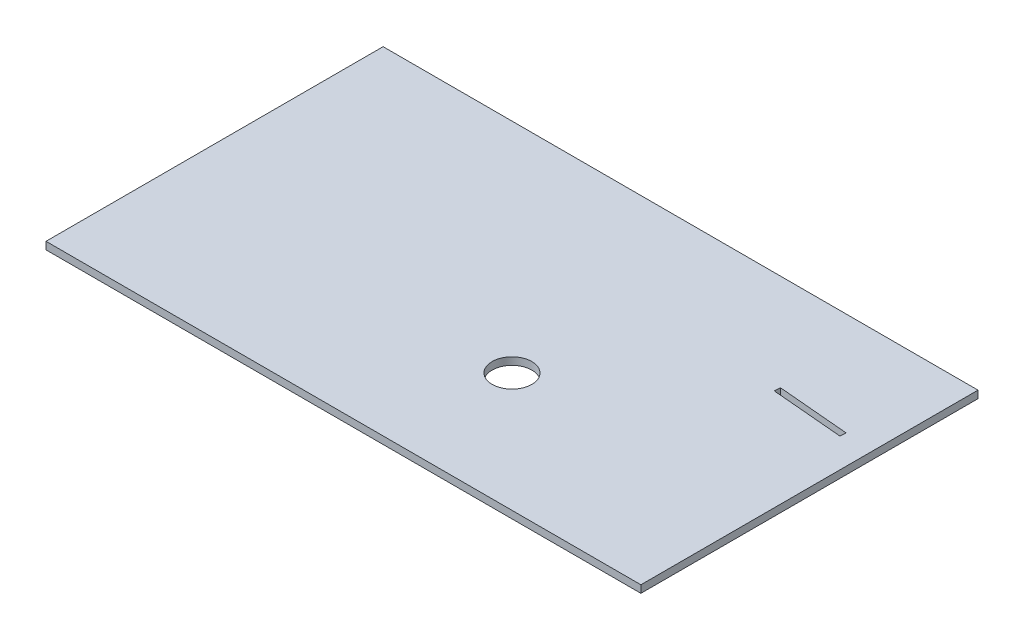
SolidWorks part; units mm, degrees
material "Particle Board"
ref_plane "Front Plane" through (0, 0, 0) normal (0, 0, 1) x (1, 0, 0)
ref_plane "Top Plane" through (0, 0, 0) normal (0, 1, 0) x (1, 0, 0)
ref_plane "Right Plane" through (0, 0, 0) normal (1, 0, 0) x (0, 0, -1)
sketch "Sketch3" plane through (0, 0, 0) normal (0, 1, 0) x (1, 0, 0)
  line L1 (0, 0) -> (-839.8654, 0) construction
  line L2 (0, 0) -> (-451.1992, 260.5) construction
  line L5 (-524, 0) -> (-525.5875, 0)
  line L6 (277.6777, 444.3772) -> (277.6777, 446.248)
  circle A0 centre (0, 0) radius 254 construction
  arc A3 (277.6777, 444.3772) -> (-524, 0) centre (0, 0) ccw
  arc A4 (277.6777, 446.248) -> (-525.5875, 0) centre (0, 0) ccw
  arc A5 (278.5189, 445.7235) -> (-525.5875, 0) centre (0, 0) ccw construction
  dimension "D1" = 524
  dimension "D2" = 1.5875
  dimension "D4" = 122
  dimension "D5" = 508
  dimension "D3" = 30
extrude "Boss-Extrude1" add sketch "Sketch3" along normal blind 50.8
sketch "Sketch4" plane through (0, 50.8, 0) normal (0, 1, 0) x (1, 0, 0)
  line L5 (-889, 558.8) -> (635, 558.8)
  line L6 (-889, 558.8) -> (-889, -304.8)
  line L7 (-889, -304.8) -> (635, -304.8)
  line L8 (635, 558.8) -> (635, -304.8)
  dimension "D1" = 304.8
  dimension "D2" = 1524
  dimension "D3" = 863.6
  dimension "D4" = 635
extrude "Boss-Extrude2" add sketch "Sketch4" along normal blind 19.05
hole_wizard "Ø20.0mm Dowel Hole1" positions "Sketch6" profile "Sketch7" hole size "Ø20.0" standard "ANSI Metric" end condition through all
sketch "Sketch6" plane through (0, 50.8, 0) normal (0, -1, 0) x (-1, 0, 0)
  point P0 (0, 0)
sketch "Sketch7" plane through (0, 50.8, 0) normal (1, 0, 0) x (0, 0, -1)
  line L0 (0, 0) -> (0, 19.05)
  line L1 (0, 19.05) -> (50.8, 19.05)
  line L2 (50.8, 19.05) -> (50.8, 0)
  line L5 (50.8, 0) -> (0, 0)
  line L11 (0, -6.35) -> (0, 107.95) construction
  dimension "Thru Hole Dia." = 101.6
  dimension "Thru Hole Depth" = 19.05
ref_plane "Plane1" through (0, 0, 298.45) normal (0, 0, 1) x (1, 0, 0)
sketch "Sketch8" plane through (0, 0, 0) normal (0, 0, 1) x (1, 0, 0)
  line L0 (-524, 50.8) -> (-524, 0) construction
  line L1 (-525.5875, 50.8) -> (-524, 50.8)
  line L2 (-525.5875, 50.8) -> (-525.5875, 0)
  line L3 (-525.5875, 0) -> (-524, 0)
  line L4 (-524, 50.8) -> (-524, 0)
  line L5 (-525.5875, 50.8) -> (-525.5875, 0) construction
  line L6 (-525.5875, 0) -> (-524, 0) construction
  line L7 (-525.5875, 50.8) -> (-524, 50.8) construction
extrude "Boss-Extrude3" add sketch "Sketch8" along normal blind 204
sketch "Sketch9" plane through (0, 50.8, 0) normal (0, -1, 0) x (-1, 0, 0)
  line L0 (-377.0113, 311.0667) -> (-561.3073, 294.9429)
  line L1 (-561.3073, 294.9429) -> (-560, 280)
  line L2 (-560, 280) -> (-375.704, 296.1238)
  line L3 (-375.704, 296.1238) -> (-377.0113, 311.0667)
  line L6 (0, 0) -> (-635, 0) construction
  line L7 (-635, -304.8) -> (-635, 558.8) construction
  dimension "D1" = 185
  dimension "D2" = 15
  dimension "D3" = 5
  dimension "D4" = 560
  dimension "D5" = 280
extrude "Cut-Extrude1" cut sketch "Sketch9" against normal through all
sketch "Sketch10" plane through (0, 69.85, 0) normal (0, -1, 0) x (-1, 0, 0)
  line L0 (0, 0) -> (-545.6, 0) construction
  line L1 (0, 0) -> (277.6777, 444.3772) construction
  line L2 (0, 0) -> (195.5256, 509.3615) construction
  line L3 (0, 0) -> (94.7424, 537.3111) construction
  circle A0 centre (0, 0) radius 545.6 construction
  dimension "D1" = 11
  dimension "D2" = 11
ref_axis "WHEEL CENTER" through (-965.2, 50.8, 0) along (1, 0, 0)
ref_plane "BASE CENTER" through (-127, 0, 0) normal (1, 0, 0) x (0, 0, -1)
sketch "Sketch11" plane through (0, 50.8, 0) normal (0, -1, 0) x (1, 0, 0)
  line L0 (240.5176, 138.2676) -> (268.3331, 149.5058)
  line L1 (268.3331, 149.5058) -> (296.8782, 78.8544)
  line L2 (296.8782, 78.8544) -> (269.0626, 67.6162)
  line L3 (269.0626, 67.6162) -> (240.5176, 138.2676)
  line L4 (-561.4964, -185.7671) -> (-532.9514, -256.4185)
  line L5 (-532.9514, -256.4185) -> (-505.1359, -245.1803)
  line L6 (-505.1359, -245.1803) -> (-533.6809, -174.5289)
  line L7 (-533.6809, -174.5289) -> (-561.4964, -185.7671)
  line L8 (-889, -266.954) -> (635, -266.954)
  line L9 (635, 304.8) -> (635, -558.8) construction
  line L10 (-889, -558.8) -> (-889, 304.8) construction
  line L11 (635, -558.8) -> (-889, -558.8) construction
  dimension "D1" = 30
  dimension "D2" = 30
  dimension "D3" = 291.846
